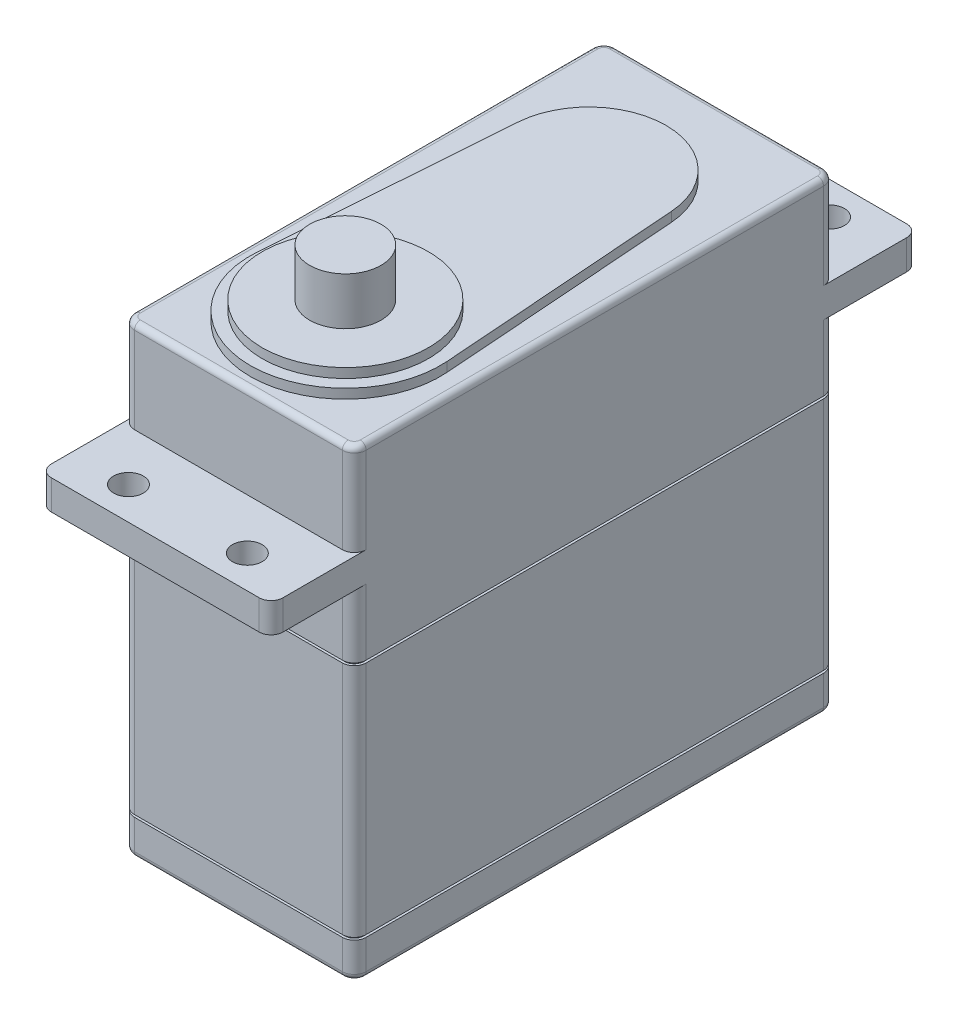
SolidWorks part; units mm, degrees
material "PET"
ref_plane "Plan de face" through (0, 0, 0) normal (0, 0, 1) x (1, 0, 0)
ref_plane "Plan de dessus" through (0, 0, 0) normal (0, 1, 0) x (1, 0, 0)
ref_plane "Plan de droite" through (0, 0, 0) normal (1, 0, 0) x (0, 0, -1)
sketch "Esquisse1" plane through (0, 0, 0) normal (1, 0, 0) x (0, 0, -1)
  line L0 (-20.25, 19.5) -> (-20.25, -19.5)
  line L1 (-20.25, -19.5) -> (20.25, -19.5) construction
  line L2 (-20.25, -19.5) -> (-20.25, 19.5) construction
  line L3 (-20.25, 19.5) -> (20.25, 19.5) construction
  line L4 (20.25, -19.5) -> (20.25, 19.5) construction
  line L5 (-20.25, -19.5) -> (20.25, 19.5) construction
  line L6 (-20.25, 19.5) -> (20.25, -19.5) construction
  line L7 (-20.25, -19.5) -> (20.25, -19.5)
  line L8 (20.25, -19.5) -> (20.25, 19.5)
  line L10 (20.25, 19.5) -> (-20.25, 19.5)
  point P0 (0, 0)
  dimension "D1" = 40.5
  dimension "D2" = 39
extrude "Boss.-Extru.1" add sketch "Esquisse1" along normal blind 9.75 and the other way blind 9.75
sketch "Esquisse2" plane through (13.65, 19.5, 0) normal (0, 1, 0) x (0, 0, -1)
  line L2 (9.7256, 20.1326) -> (-10.6646, 21.6286)
  line L8 (9.7256, 7.1674) -> (-10.6646, 5.6714)
  line L10 (-20.25, 23.4) -> (-20.25, 3.9) construction
  line L11 (-21.9192, 13.65) -> (21.2753, 13.65) construction
  line L12 (-11.25, 1.5484) -> (-11.25, 25.1271) construction
  arc A0 (-10.6646, 21.6286) -> (-10.6646, 5.6714) centre (-11.25, 13.65) ccw
  arc A1 (9.7256, 20.1326) -> (9.7256, 7.1674) centre (9.25, 13.65) cw
  dimension "D2" = 9
  dimension "D3" = 8
  dimension "D4" = 6.5
  dimension "D1" = 27
extrude "Boss.-Extru.2" add sketch "Esquisse2" along normal blind 0.8
ref_axis "Axe1" through (0, 26.1544, 11.25) along (0, -1, 0)
sketch "Esquisse3" plane through (0, 0, 0) normal (1, 0, 0) x (0, 0, -1)
  line L0 (-11.25, 19.89) -> (-11.25, 16.0263) construction
  line L2 (-4.25, 20.3) -> (-4.25, 21.1)
  line L4 (-4.25, 21.1) -> (-8.25, 21.1)
  line L5 (-8.25, 21.1) -> (-8.25, 25.1)
  line L6 (-8.25, 25.1) -> (-11.25, 25.1)
  line L7 (-11.25, 25.1) -> (-11.25, 20.3)
  line L8 (-11.25, 20.3) -> (-4.25, 20.3)
  line L11 (-11.25, 26.1544) -> (-11.25, 19.5) construction
  line L12 (9.7256, 20.3) -> (-10.6646, 20.3) construction
  dimension "D2" = 14
  dimension "D3" = 6
  dimension "D4" = 0.8
  dimension "D5" = 4
revolve "Révolution1" add sketch "Esquisse3" angle 360 about L0
fillet "Congé6" radius 1 4 edges at (9.75, 0, 20.25) (9.75, 0, -20.25) (-9.75, 0, 20.25) (-9.75, 0, -20.25) tangent propagation no
fillet "Congé3" radius 0.5 16 edges at (0, -19.5, -20.25) (-9.75, -19.5, 0) (0, -19.5, 20.25) (9.75, -19.5, 0) (-9.75, 19.5, 0) (0, 19.5, 20.25) (9.75, 19.5, 0) (0, 19.5, -20.25) (9.4571, -19.5, -19.9571) (-9.4571, -19.5, -19.9571) (-9.4571, -19.5, 19.9571) (9.4571, -19.5, 19.9571) (-9.4571, 19.5, -19.9571) (-9.4571, 19.5, 19.9571) (9.4571, 19.5, 19.9571) (9.4571, 19.5, -19.9571)
ref_plane "Plan1" through (0, -16.5, 0) normal (0, -1, 0) x (-1, 0, 0)
ref_plane "Plan2" through (0, 3.5, 0) normal (0, -1, 0) x (-1, 0, 0)
sketch "Esquisse7" plane through (0, -16.5, 0) normal (0, -1, 0) x (-1, 0, 0)
  line L0 (8.75, -20.25) -> (-8.75, -20.25) construction
  line L1 (-9.75, -19.25) -> (-9.75, 19.25) construction
  line L2 (9.75, 19.25) -> (9.75, -19.25) construction
  line L3 (-8.75, 20.25) -> (8.75, 20.25) construction
  line L4 (8.75, -20.25) -> (-8.75, -20.25)
  line L5 (-9.75, -19.25) -> (-9.75, 19.25)
  line L6 (9.75, 19.25) -> (9.75, -19.25)
  line L7 (-8.75, 20.25) -> (8.75, 20.25)
  line L8 (8.75, -20.05) -> (-8.75, -20.05)
  line L9 (-9.55, -19.25) -> (-9.55, 19.25)
  line L10 (-8.75, 20.05) -> (8.75, 20.05)
  line L11 (9.55, 19.25) -> (9.55, -19.25)
  arc A0 (8.75, -20.25) -> (9.75, -19.25) centre (8.75, -19.25) ccw construction
  arc A1 (-9.75, -19.25) -> (-8.75, -20.25) centre (-8.75, -19.25) ccw construction
  arc A2 (-8.75, 20.25) -> (-9.75, 19.25) centre (-8.75, 19.25) ccw construction
  arc A3 (9.75, 19.25) -> (8.75, 20.25) centre (8.75, 19.25) ccw construction
  arc A4 (8.75, -20.25) -> (9.75, -19.25) centre (8.75, -19.25) ccw
  arc A5 (-9.75, -19.25) -> (-8.75, -20.25) centre (-8.75, -19.25) ccw
  arc A6 (-8.75, 20.25) -> (-9.75, 19.25) centre (-8.75, 19.25) ccw
  arc A7 (9.75, 19.25) -> (8.75, 20.25) centre (8.75, 19.25) ccw
  arc A8 (-9.55, -19.25) -> (-8.75, -20.05) centre (-8.75, -19.25) ccw
  arc A9 (-8.75, 20.05) -> (-9.55, 19.25) centre (-8.75, 19.25) ccw
  arc A10 (9.55, 19.25) -> (8.75, 20.05) centre (8.75, 19.25) ccw
  arc A11 (8.75, -20.05) -> (9.55, -19.25) centre (8.75, -19.25) ccw
  dimension "D1" = 0.2
extrude "Enlèv. mat.-Extru.3" cut sketch "Esquisse7" against normal blind 0.2
sketch "Esquisse6" plane through (0, 3.5, 0) normal (0, -1, 0) x (-1, 0, 0)
  line L0 (8.75, -20.05) -> (-8.75, -20.05)
  line L1 (-9.55, -19.25) -> (-9.55, 19.25)
  line L2 (-8.75, 20.05) -> (8.75, 20.05)
  line L3 (9.55, 19.25) -> (9.55, -19.25)
  line L4 (8.75, -20.25) -> (-8.75, -20.25) construction
  line L5 (-9.75, -19.25) -> (-9.75, 19.25) construction
  line L6 (9.75, 19.25) -> (9.75, -19.25) construction
  line L7 (-8.75, 20.25) -> (8.75, 20.25) construction
  line L8 (8.75, -20.25) -> (-8.75, -20.25)
  line L9 (-9.75, -19.25) -> (-9.75, 19.25)
  line L10 (9.75, 19.25) -> (9.75, -19.25)
  line L11 (-8.75, 20.25) -> (8.75, 20.25)
  arc A0 (-9.55, -19.25) -> (-8.75, -20.05) centre (-8.75, -19.25) ccw
  arc A1 (-8.75, 20.05) -> (-9.55, 19.25) centre (-8.75, 19.25) ccw
  arc A2 (9.55, 19.25) -> (8.75, 20.05) centre (8.75, 19.25) ccw
  arc A3 (8.75, -20.05) -> (9.55, -19.25) centre (8.75, -19.25) ccw
  arc A4 (8.75, -20.25) -> (9.75, -19.25) centre (8.75, -19.25) ccw construction
  arc A5 (-9.75, -19.25) -> (-8.75, -20.25) centre (-8.75, -19.25) ccw construction
  arc A6 (-8.75, 20.25) -> (-9.75, 19.25) centre (-8.75, 19.25) ccw construction
  arc A7 (9.75, 19.25) -> (8.75, 20.25) centre (8.75, 19.25) ccw construction
  arc A8 (8.75, -20.25) -> (9.75, -19.25) centre (8.75, -19.25) ccw
  arc A9 (-9.75, -19.25) -> (-8.75, -20.25) centre (-8.75, -19.25) ccw
  arc A10 (-8.75, 20.25) -> (-9.75, 19.25) centre (-8.75, 19.25) ccw
  arc A11 (9.75, 19.25) -> (8.75, 20.25) centre (8.75, 19.25) ccw
  dimension "D1" = 0.2
extrude "Enlèv. mat.-Extru.2" cut sketch "Esquisse6" against normal blind 0.2
ref_plane "Plan3" through (0, 10.5, 0) normal (0, -1, 0) x (-1, 0, 0)
sketch "Esquisse8" plane through (0, 10.5, 0) normal (0, -1, 0) x (-1, 0, 0)
  line L0 (-9.75, 19.25) -> (-9.75, -19.25) construction
  line L2 (9.75, 19.25) -> (9.75, 26.25)
  line L3 (8.75, 27.25) -> (-8.75, 27.25)
  line L4 (-9.75, 26.25) -> (-9.75, 19.25)
  line L5 (-8.75, 20.25) -> (8.75, 20.25)
  line L6 (9.75, -19.25) -> (9.75, 19.25) construction
  line L7 (8.75, 20.25) -> (-8.75, 20.25) construction
  arc A0 (-8.75, 20.25) -> (-9.75, 19.25) centre (-8.75, 19.25) ccw construction
  arc A2 (9.75, 19.25) -> (8.75, 20.25) centre (8.75, 19.25) ccw construction
  arc A4 (9.75, 26.25) -> (8.75, 27.25) centre (8.75, 26.25) ccw
  arc A5 (-8.75, 27.25) -> (-9.75, 26.25) centre (-8.75, 26.25) ccw
  arc A6 (9.75, 19.25) -> (8.75, 20.25) centre (8.75, 19.25) ccw
  arc A7 (-8.75, 20.25) -> (-9.75, 19.25) centre (-8.75, 19.25) ccw
  point P1 (29.0042, 19.4685)
  point P6 (28.2909, 20.1837)
  point P13 (-10.5277, 21.914)
  point P17 (11.6061, 20.4126)
  point P18 (13.6628, 30.1829)
  point P19 (10.6635, 21.3563)
  point P20 (10.7492, 21.7848)
  point P21 (12.206, 23.3273)
  point P22 (3.8079, 22.1276)
  point P23 (10.1493, 22.1276)
  point P26 (-8.75, 21.6704)
  point P27 (-9.4571, 20.8847)
  dimension "D1" = 1
  dimension "D2" = 7
extrude "Boss.-Extru.3" add sketch "Esquisse8" against normal blind 1.25 and the other way blind 1.25
sketch "Esquisse10" plane through (0, 11.75, 0) normal (0, 1, 0) x (1, 0, 0)
  circle A0 centre (5, 24.5) radius 1.25
  dimension "D1" = 24.5
  dimension "D2" = 5
extrude "Enlèv. mat.-Extru.4" cut sketch "Esquisse10" against normal up to next
mirror "Symétrie1" about plane through (0, 0, 0) normal (0, 0, 1) of "Boss.-Extru.3"
mirror "Symétrie2" about plane through (0, 0, 0) normal (1, 0, 0) of "Enlèv. mat.-Extru.4"
mirror "Symétrie3" about plane through (0, 0, 0) normal (0, 0, 1) of "Symétrie2"
